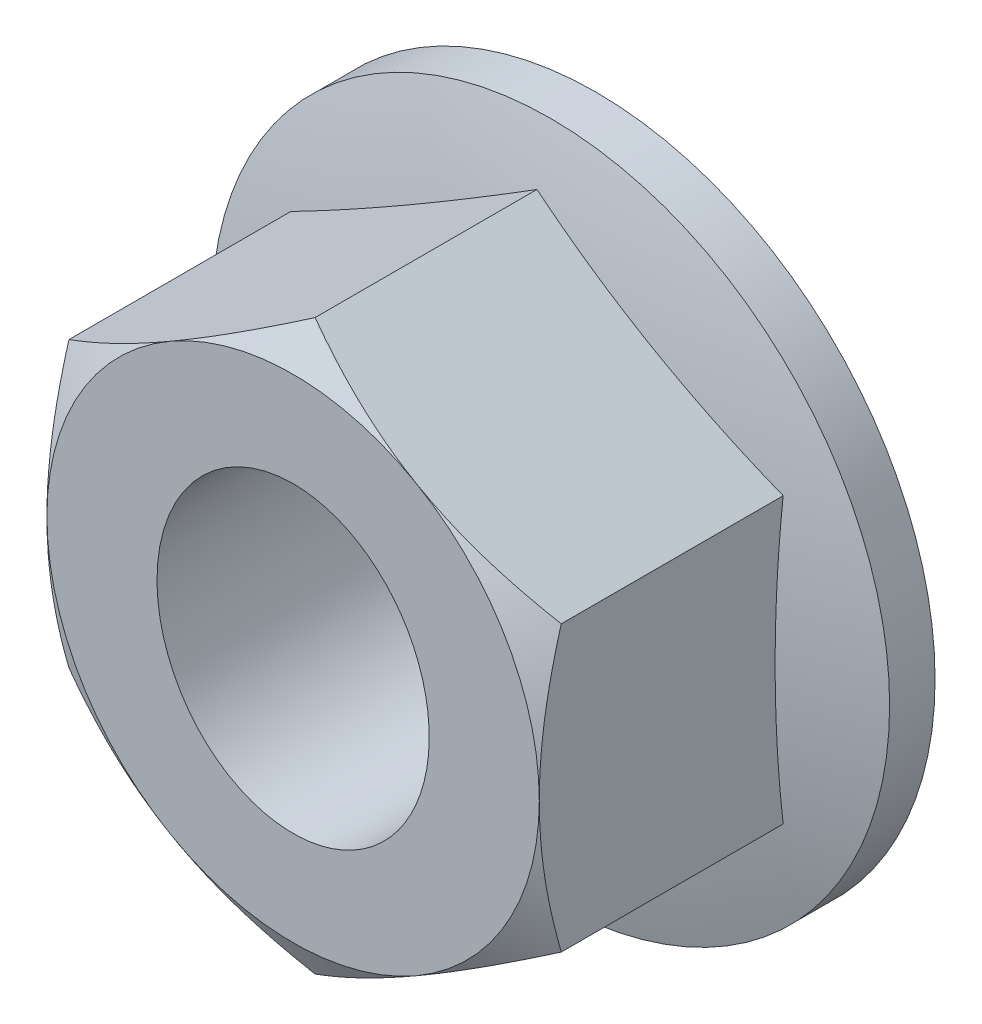
SolidWorks part; units mm, degrees
ref_plane "Front" through (0, 0, 0) normal (0, 0, 1) x (1, 0, 0)
ref_plane "Top" through (0, 0, 0) normal (0, 1, 0) x (1, 0, 0)
ref_plane "Right" through (0, 0, 0) normal (1, 0, 0) x (0, 0, -1)
sketch "Sketch1" plane through (0, 0, 0) normal (0, 0, 1) x (1, 0, 0)
  line L1 (6.5, -3.7528) -> (6.5, 3.7528)
  line L2 (6.5, 3.7528) -> (0, 7.5056)
  line L3 (0, 7.5056) -> (-6.5, 3.7528)
  line L4 (-6.5, 3.7528) -> (-6.5, -3.7528)
  line L5 (-6.5, -3.7528) -> (0, -7.5056)
  line L6 (0, -7.5056) -> (6.5, -3.7528)
  circle A0 centre (0, 0) radius 6.5 construction
  circle A1 centre (0, 0) radius 8.95 construction
  point P10 (0, 8.95)
  dimension "Flange OD" = 17.9
  dimension "Hex" = 13
extrude "Extrude1" add sketch "Sketch1" along normal mid plane 8
sketch "Sketch18" plane through (0, 0, 0) normal (1, 0, 0) x (0, 0, -1)
  line L0 (4, 0) -> (4, 8.95)
  line L1 (4, 8.95) -> (2.8, 8.95)
  line L2 (1.6, 0) -> (4, 0) construction
  line L3 (1.6, 0) -> (1.6, 8.95) construction
  line L4 (4, -3.7528) -> (4, 3.7528) construction
  line L5 (2.8, 8.95) -> (2.8, 0) construction
  line L6 (4, 0) -> (1.6, 0)
  arc A0 (2.8, 8.95) -> (1.6, 0) centre (35.576, 0) ccw
  dimension "Flange Thickness" = 1.2
revolve "Revolve1" add sketch "Sketch18" angle 360 about L6
sketch "Sketch2" plane through (0, 0, 4) normal (0, 0, 1) x (1, 0, 0)
  circle A0 centre (0, 0) radius 6.5 construction
  circle A5 centre (0, 0) radius 6.5
extrude "Cut-Extrude1" cut sketch "Sketch2" against normal through all draft 60 flip side to cut
sketch "Sketch4" plane through (0, 0, -4) normal (0, 0, -1) x (-1, 0, 0)
  line L0 (4, 0) -> (3.5941, 0) construction
  circle A0 centre (0, 0) radius 4
  circle A1 centre (0, 0) radius 3.5941 construction
  dimension "Thread OD" = 8
  dimension "D1" = 0.4059
sketch "Sketch5" plane through (0, 0, 4) normal (0, 0, -1) x (-1, 0, 0)
  circle A2 centre (0, 0) radius 4 construction
  circle A3 centre (0, 0) radius 4
sketch "Sketch7" plane through (0, 0, -4) normal (0, 0, -1) x (-1, 0, 0)
  circle A0 centre (0, 0) radius 4 construction
  circle A1 centre (0, 0) radius 4
curve "Helix/Spiral1" pitch 1.25 height 9.25 turns 7.4 parameters "pitch"=1.25
extrude "Cut-Extrude10" cut sketch "Sketch5" along normal through all
sketch "Sketch16" plane through (0, 0, 4) normal (0, 0, 1) x (1, 0, 0)
  circle A0 centre (0, 0) radius 6.5
  circle A1 centre (0, 0) radius 6.5 construction
  circle A2 centre (0, 0) radius 4 construction
  circle A3 centre (0, 0) radius 3.5941 construction
  ellipse E0 centre (0, 0) end of major axis (0, 4) minor radius 3.5941
extrude "Extrude2" add sketch "Sketch16" against normal up to surface (8 mm away) up to face at (0, 8.95, -4)
sketch "Sketch9" [suppressed] plane through (0, 0, -7.9375) normal (1, 0, 0) x (0, 0, -1)
  line L0 (-3.9375, 4) -> (-2.8438, 4)
  line L1 (-2.8438, 4) -> (-3.3125, 3.1881)
  line L2 (-3.3125, 3.1881) -> (-3.4687, 3.1881)
  line L3 (-3.4687, 3.1881) -> (-3.9375, 4)
  line L4 (-3.3906, 3.1881) -> (-3.3906, 4) construction
  line L5 (-3.7031, 3.5941) -> (-3.0781, 3.5941) construction
  line L6 (-3.9375, -4) -> (-3.9375, 4) construction
  dimension "D1" = 0.625
  dimension "D2" = 0.1562
  dimension "D3" = 60
  dimension "D4" = 0.8119
sweep "Sweep1" [suppressed] add profiles "Sketch9" path "Helix/Spiral1"
sketch "Sketch10" [suppressed] plane through (0, 0, -4) normal (0, 0, -1) x (-1, 0, 0)
  line L6 (-6.5, 3.7528) -> (-6.5, -3.7528)
  line L7 (0, 7.5056) -> (-6.5, 3.7528)
  line L8 (6.5, 3.7528) -> (0, 7.5056)
  line L9 (6.5, -3.7528) -> (6.5, 3.7528)
  line L10 (0, -7.5056) -> (6.5, -3.7528)
  line L11 (-6.5, -3.7528) -> (0, -7.5056)
  line L12 (-6.5, 3.7528) -> (-6.5, -3.7528)
  line L13 (0, 7.5056) -> (-6.5, 3.7528)
  line L14 (6.5, 3.7528) -> (0, 7.5056)
  line L15 (6.5, -3.7528) -> (6.5, 3.7528)
  line L16 (0, -7.5056) -> (6.5, -3.7528)
  line L17 (-6.5, -3.7528) -> (0, -7.5056)
  dimension "D1" = 0
extrude "Cut-Extrude4" [suppressed] cut sketch "Sketch10" along normal through all
sketch "Sketch11" [suppressed] plane through (0, 0, 4) normal (0, 0, 1) x (1, 0, 0)
  line L6 (6.5, -3.7528) -> (6.5, 3.7528)
  line L7 (6.5, 3.7528) -> (0, 7.5056)
  line L8 (0, 7.5056) -> (-6.5, 3.7528)
  line L9 (-6.5, 3.7528) -> (-6.5, -3.7528)
  line L10 (-6.5, -3.7528) -> (0, -7.5056)
  line L11 (0, -7.5056) -> (6.5, -3.7528)
  line L12 (6.5, -3.7528) -> (6.5, 3.7528)
  line L13 (6.5, 3.7528) -> (0, 7.5056)
  line L14 (0, 7.5056) -> (-6.5, 3.7528)
  line L15 (-6.5, 3.7528) -> (-6.5, -3.7528)
  line L16 (-6.5, -3.7528) -> (0, -7.5056)
  line L17 (0, -7.5056) -> (6.5, -3.7528)
  dimension "D1" = 0
extrude "Cut-Extrude5" [suppressed] cut sketch "Sketch11" along normal through all
sketch "Sketch13" [suppressed] plane through (0, 0, 4) normal (0, 0, 1) x (1, 0, 0)
  spline S0 degree 3 poles (-0.2563, -4.0762) (0.2563, -4.0762) (0.5075, -4.0467) (1.0002, -3.9319) (1.2437, -3.845) (1.6991, -3.6237) (1.9138, -3.4891) (2.3168, -3.1735) (2.4988, -2.9975) (2.8277, -2.6124) (2.9752, -2.4012) (3.2263, -1.9609) (3.3311, -1.7309) (3.5006, -1.2517) (3.5646, -1.0034) (3.6491, -0.5054) (3.6703, -0.2536) (3.6702, 0.2559) (3.6485, 0.51) (3.5638, 1.0069) (3.5008, 1.2514) (3.3308, 1.7317) (3.2248, 1.9636) (2.9754, 2.4008) (2.8313, 2.6077) (2.5005, 2.9959) (2.317, 3.1729) (1.9212, 3.4837) (1.7071, 3.6193) (1.2471, 3.8439) (1.0092, 3.929) (0.5179, 4.045) (0.261, 4.0756) (-0.2461, 4.0768) (-0.4974, 4.0485) (-0.9953, 3.9336) (-1.2361, 3.8481) (-1.6921, 3.6277) (-1.9111, 3.4907) (-2.3111, 3.1783) (-2.4938, 3.0028) (-2.826, 2.6148) (-2.9723, 2.4057) (-3.2236, 1.9663) (-3.3302, 1.733) (-3.5002, 1.2532) (-3.5635, 1.0084) (-3.6487, 0.5093) (-3.6703, 0.2527) (-3.6702, -0.2544) (-3.649, -0.5059) (-3.5644, -1.0048) (-3.4998, -1.2543) (-3.3307, -1.7317) (-3.2262, -1.9609) (-2.9759, -2.4) (-2.8281, -2.6118) (-2.4995, -2.9968) (-2.3184, -3.1718) (-1.9205, -3.4843) (-1.7013, -3.6224) (-1.2469, -3.8437) (-1.0094, -3.9292) (-0.5126, -4.0461) (-0.2563, -4.0762) (0.2563, -4.0762) (0.5075, -4.0467) knots -0.03125 -0.03125 0 0 0.03125 0.03125 0.0625 0.0625 0.09375 0.09375 0.125 0.125 0.15625 0.15625 0.1875 0.1875 0.21875 0.21875 0.25 0.25 0.28125 0.28125 0.3125 0.3125 0.34375 0.34375 0.375 0.375 0.40625 0.40625 0.4375 0.4375 0.46875 0.46875 0.5 0.5 0.53125 0.53125 0.5625 0.5625 0.59375 0.59375 0.625 0.625 0.65625 0.65625 0.6875 0.6875 0.71875 0.71875 0.75 0.75 0.78125 0.78125 0.8125 0.8125 0.84375 0.84375 0.875 0.875 0.90625 0.90625 0.9375 0.9375 0.96875 0.96875 1 1 1.03125 1.03125 1.0625 only from (0, -4.0762) to (0, -4.0762)
  spline S1 degree 3 poles (-0.2563, -4.0762) (0.2563, -4.0762) (0.5075, -4.0467) (1.0002, -3.9319) (1.2437, -3.845) (1.6991, -3.6237) (1.9138, -3.4891) (2.3168, -3.1735) (2.4988, -2.9975) (2.8277, -2.6124) (2.9752, -2.4012) (3.2263, -1.9609) (3.3311, -1.7309) (3.5006, -1.2517) (3.5646, -1.0034) (3.6491, -0.5054) (3.6703, -0.2536) (3.6702, 0.2559) (3.6485, 0.51) (3.5638, 1.0069) (3.5008, 1.2514) (3.3308, 1.7317) (3.2248, 1.9636) (2.9754, 2.4008) (2.8313, 2.6077) (2.5005, 2.9959) (2.317, 3.1729) (1.9212, 3.4837) (1.7071, 3.6193) (1.2471, 3.8439) (1.0092, 3.929) (0.5179, 4.045) (0.261, 4.0756) (-0.2461, 4.0768) (-0.4974, 4.0485) (-0.9953, 3.9336) (-1.2361, 3.8481) (-1.6921, 3.6277) (-1.9111, 3.4907) (-2.3111, 3.1783) (-2.4938, 3.0028) (-2.826, 2.6148) (-2.9723, 2.4057) (-3.2236, 1.9663) (-3.3302, 1.733) (-3.5002, 1.2532) (-3.5635, 1.0084) (-3.6487, 0.5093) (-3.6703, 0.2527) (-3.6702, -0.2544) (-3.649, -0.5059) (-3.5644, -1.0048) (-3.4998, -1.2543) (-3.3307, -1.7317) (-3.2262, -1.9609) (-2.9759, -2.4) (-2.8281, -2.6118) (-2.4995, -2.9968) (-2.3184, -3.1718) (-1.9205, -3.4843) (-1.7013, -3.6224) (-1.2469, -3.8437) (-1.0094, -3.9292) (-0.5126, -4.0461) (-0.2563, -4.0762) (0.2563, -4.0762) (0.5075, -4.0467) knots -0.03125 -0.03125 0 0 0.03125 0.03125 0.0625 0.0625 0.09375 0.09375 0.125 0.125 0.15625 0.15625 0.1875 0.1875 0.21875 0.21875 0.25 0.25 0.28125 0.28125 0.3125 0.3125 0.34375 0.34375 0.375 0.375 0.40625 0.40625 0.4375 0.4375 0.46875 0.46875 0.5 0.5 0.53125 0.53125 0.5625 0.5625 0.59375 0.59375 0.625 0.625 0.65625 0.65625 0.6875 0.6875 0.71875 0.71875 0.75 0.75 0.78125 0.78125 0.8125 0.8125 0.84375 0.84375 0.875 0.875 0.90625 0.90625 0.9375 0.9375 0.96875 0.96875 1 1 1.03125 1.03125 1.0625 only from (0, -4.0762) to (0, -4.0762)
  dimension "D1" = 0.0762
extrude "Cut-Extrude8" [suppressed] cut sketch "Sketch13" against normal blind 2.1875 draft 45
sketch "Sketch14" [suppressed] plane through (0, 0, -4) normal (0, 0, -1) x (-1, 0, 0)
  spline S1 degree 3 poles (-0.2563, -4.0762) (0.2563, -4.0762) (0.5126, -4.0461) (1.0094, -3.9292) (1.2469, -3.8437) (1.7013, -3.6224) (1.9205, -3.4843) (2.3184, -3.1718) (2.4995, -2.9968) (2.8281, -2.6118) (2.9759, -2.4) (3.2262, -1.9609) (3.3307, -1.7317) (3.4998, -1.2543) (3.5644, -1.0048) (3.649, -0.5059) (3.6702, -0.2544) (3.6703, 0.2527) (3.6487, 0.5093) (3.5635, 1.0084) (3.5002, 1.2532) (3.3302, 1.733) (3.2236, 1.9663) (2.9723, 2.4057) (2.826, 2.6148) (2.4938, 3.0028) (2.3111, 3.1783) (1.9111, 3.4907) (1.6921, 3.6277) (1.2361, 3.8481) (0.9953, 3.9336) (0.4974, 4.0485) (0.2461, 4.0768) (-0.261, 4.0756) (-0.5179, 4.045) (-1.0092, 3.929) (-1.2471, 3.8439) (-1.7071, 3.6193) (-1.9212, 3.4837) (-2.317, 3.1729) (-2.5005, 2.9959) (-2.8313, 2.6077) (-2.9754, 2.4008) (-3.2248, 1.9636) (-3.3308, 1.7317) (-3.5008, 1.2514) (-3.5638, 1.0069) (-3.6485, 0.51) (-3.6702, 0.2559) (-3.6703, -0.2536) (-3.6491, -0.5054) (-3.5646, -1.0034) (-3.5006, -1.2517) (-3.3311, -1.7309) (-3.2263, -1.9609) (-2.9752, -2.4012) (-2.8277, -2.6124) (-2.4988, -2.9975) (-2.3168, -3.1735) (-1.9138, -3.4891) (-1.6991, -3.6237) (-1.2437, -3.845) (-1.0002, -3.9319) (-0.5075, -4.0467) (-0.2563, -4.0762) (0.2563, -4.0762) (0.5126, -4.0461) knots -0.03125 -0.03125 0 0 0.03125 0.03125 0.0625 0.0625 0.09375 0.09375 0.125 0.125 0.15625 0.15625 0.1875 0.1875 0.21875 0.21875 0.25 0.25 0.28125 0.28125 0.3125 0.3125 0.34375 0.34375 0.375 0.375 0.40625 0.40625 0.4375 0.4375 0.46875 0.46875 0.5 0.5 0.53125 0.53125 0.5625 0.5625 0.59375 0.59375 0.625 0.625 0.65625 0.65625 0.6875 0.6875 0.71875 0.71875 0.75 0.75 0.78125 0.78125 0.8125 0.8125 0.84375 0.84375 0.875 0.875 0.90625 0.90625 0.9375 0.9375 0.96875 0.96875 1 1 1.03125 1.03125 1.0625 only from (0, -4.0762) to (0, -4.0762)
  spline S2 degree 3 poles (-0.2563, -4.0762) (0.2563, -4.0762) (0.5126, -4.0461) (1.0094, -3.9292) (1.2469, -3.8437) (1.7013, -3.6224) (1.9205, -3.4843) (2.3184, -3.1718) (2.4995, -2.9968) (2.8281, -2.6118) (2.9759, -2.4) (3.2262, -1.9609) (3.3307, -1.7317) (3.4998, -1.2543) (3.5644, -1.0048) (3.649, -0.5059) (3.6702, -0.2544) (3.6703, 0.2527) (3.6487, 0.5093) (3.5635, 1.0084) (3.5002, 1.2532) (3.3302, 1.733) (3.2236, 1.9663) (2.9723, 2.4057) (2.826, 2.6148) (2.4938, 3.0028) (2.3111, 3.1783) (1.9111, 3.4907) (1.6921, 3.6277) (1.2361, 3.8481) (0.9953, 3.9336) (0.4974, 4.0485) (0.2461, 4.0768) (-0.261, 4.0756) (-0.5179, 4.045) (-1.0092, 3.929) (-1.2471, 3.8439) (-1.7071, 3.6193) (-1.9212, 3.4837) (-2.317, 3.1729) (-2.5005, 2.9959) (-2.8313, 2.6077) (-2.9754, 2.4008) (-3.2248, 1.9636) (-3.3308, 1.7317) (-3.5008, 1.2514) (-3.5638, 1.0069) (-3.6485, 0.51) (-3.6702, 0.2559) (-3.6703, -0.2536) (-3.6491, -0.5054) (-3.5646, -1.0034) (-3.5006, -1.2517) (-3.3311, -1.7309) (-3.2263, -1.9609) (-2.9752, -2.4012) (-2.8277, -2.6124) (-2.4988, -2.9975) (-2.3168, -3.1735) (-1.9138, -3.4891) (-1.6991, -3.6237) (-1.2437, -3.845) (-1.0002, -3.9319) (-0.5075, -4.0467) (-0.2563, -4.0762) (0.2563, -4.0762) (0.5126, -4.0461) knots -0.03125 -0.03125 0 0 0.03125 0.03125 0.0625 0.0625 0.09375 0.09375 0.125 0.125 0.15625 0.15625 0.1875 0.1875 0.21875 0.21875 0.25 0.25 0.28125 0.28125 0.3125 0.3125 0.34375 0.34375 0.375 0.375 0.40625 0.40625 0.4375 0.4375 0.46875 0.46875 0.5 0.5 0.53125 0.53125 0.5625 0.5625 0.59375 0.59375 0.625 0.625 0.65625 0.65625 0.6875 0.6875 0.71875 0.71875 0.75 0.75 0.78125 0.78125 0.8125 0.8125 0.84375 0.84375 0.875 0.875 0.90625 0.90625 0.9375 0.9375 0.96875 0.96875 1 1 1.03125 1.03125 1.0625 only from (0, -4.0762) to (0, -4.0762)
  dimension "D1" = 0
extrude "Cut-Extrude9" [suppressed] cut sketch "Sketch14" against normal blind 2.1875 draft 45
ref_plane "Contact Plane 1" through (0, 0, -4) normal (0, 0, -1) x (-1, 0, 0)
ref_axis "Center Axis 1" through (0, 0, 50) along (0, 0, -1)
equation "\"D1@Sketch9\" = \"pitch@Helix/Spiral1\"*.5"
equation "\"D2@Sketch9\" = \"pitch@Helix/Spiral1\"*.125"
equation "\"D3@Helix/Spiral1\"=\"height@Extrude1\"+\"pitch@Helix/Spiral1\""
equation "\"D1@Cut-Extrude8\" = \"pitch@Helix/Spiral1\"*1.750"
equation "\"D1@Cut-Extrude9\" = \"D1@Cut-Extrude8\""
equation "\"D1@Sketch4\" = \"D4@Sketch9\"*.5"
